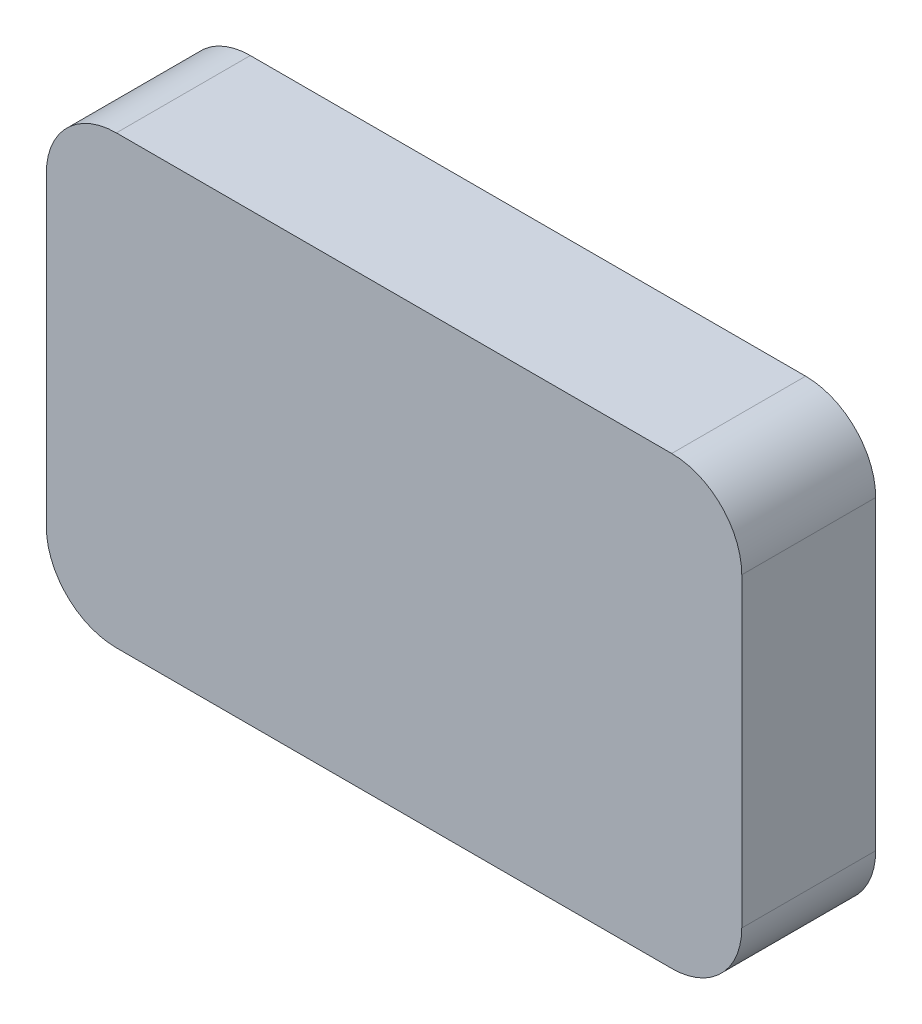
SolidWorks part; units mm, degrees
ref_plane "Plan de face" through (0, 0, 0) normal (0, 0, 1) x (1, 0, 0)
ref_plane "Plan de dessus" through (0, 0, 0) normal (0, 1, 0) x (1, 0, 0)
ref_plane "Plan de droite" through (0, 0, 0) normal (1, 0, 0) x (0, 0, -1)
sketch "Esquisse1" plane through (0, 0, 0) normal (0, 0, 1) x (1, 0, 0)
  line L1 (-39.6342, 31.8306) -> (39.6342, 31.8306)
  line L2 (-49.6342, 21.8306) -> (-49.6342, -21.8306)
  line L3 (-39.6342, -31.8306) -> (39.6342, -31.8306)
  line L4 (49.6342, 21.8306) -> (49.6342, -21.8306)
  line L5 (-49.6342, 31.8306) -> (49.6342, -31.8306) construction
  line L6 (-49.6342, -31.8306) -> (49.6342, 31.8306) construction
  arc A0 (-49.6342, -21.8306) -> (-39.6342, -31.8306) centre (-39.6342, -21.8306) ccw
  arc A1 (39.6342, -31.8306) -> (49.6342, -21.8306) centre (39.6342, -21.8306) ccw
  arc A2 (39.6342, 31.8306) -> (49.6342, 21.8306) centre (39.6342, 21.8306) cw
  arc A3 (-39.6342, 31.8306) -> (-49.6342, 21.8306) centre (-39.6342, 21.8306) ccw
  point P0 (0, 0)
  dimension "D1" = 10
sketch "profil" plane through (0, 0, 0) normal (1, 0, 0) x (0, 0, -1)
  line L0 (0, -30.2306) -> (9.1225, -30.2306)
  line L1 (9.1225, -30.2306) -> (17.9182, -25.6306)
  line L3 (17.9182, -31.8306) -> (0, -31.8306)
  line L4 (0, -31.8306) -> (0, -30.2306)
  line L6 (0, -21.8306) -> (0, -31.8306) construction
  line L7 (0, -31.8306) -> (0, 31.8306) construction
  line L8 (17.9182, -25.6306) -> (17.9182, -27.2306)
  line L9 (17.9182, -30.2306) -> (17.9182, -31.8306)
  arc A0 (17.9182, -27.2306) -> (17.9182, -30.2306) centre (17.9182, -28.7306) ccw
  dimension "D1" = 3
  dimension "D2" = 1.6
sweep "Balayage1" add profiles "profil" path "Esquisse1"
extrude "Boss.-Extru.1" add sketch "Esquisse1<3>" along normal blind 1.2
sketch "Esquisse1<3>" plane through (0, 0, 0) normal (0, 0, 1) x (1, 0, 0) same geometry as "Esquisse1"
fillet "Congé1" radius 2 9 edges at (-45.5739, 27.7703, 0) (-48.0342, 0, 0) (-45.5739, -27.7703, 0) (-19.8171, -30.2306, 0) (19.8171, -30.2306, 0) (45.5739, -27.7703, 0) (48.0342, 0, 0) (45.5739, 27.7703, 0) (0, 30.2306, 0)
equation "\"buse\"=0.4"
equation "\"coque\"= \"buse\" * 4"
equation "\"diam_silicone\"=3"
equation "\"D1@profil\" = \"diam_silicone\""
equation "\"couche\"=0.2"
equation "\"D1@Boss.-Extru.1\"=\"fond\""
equation "\"fond\"= \"couche\" * 6"
